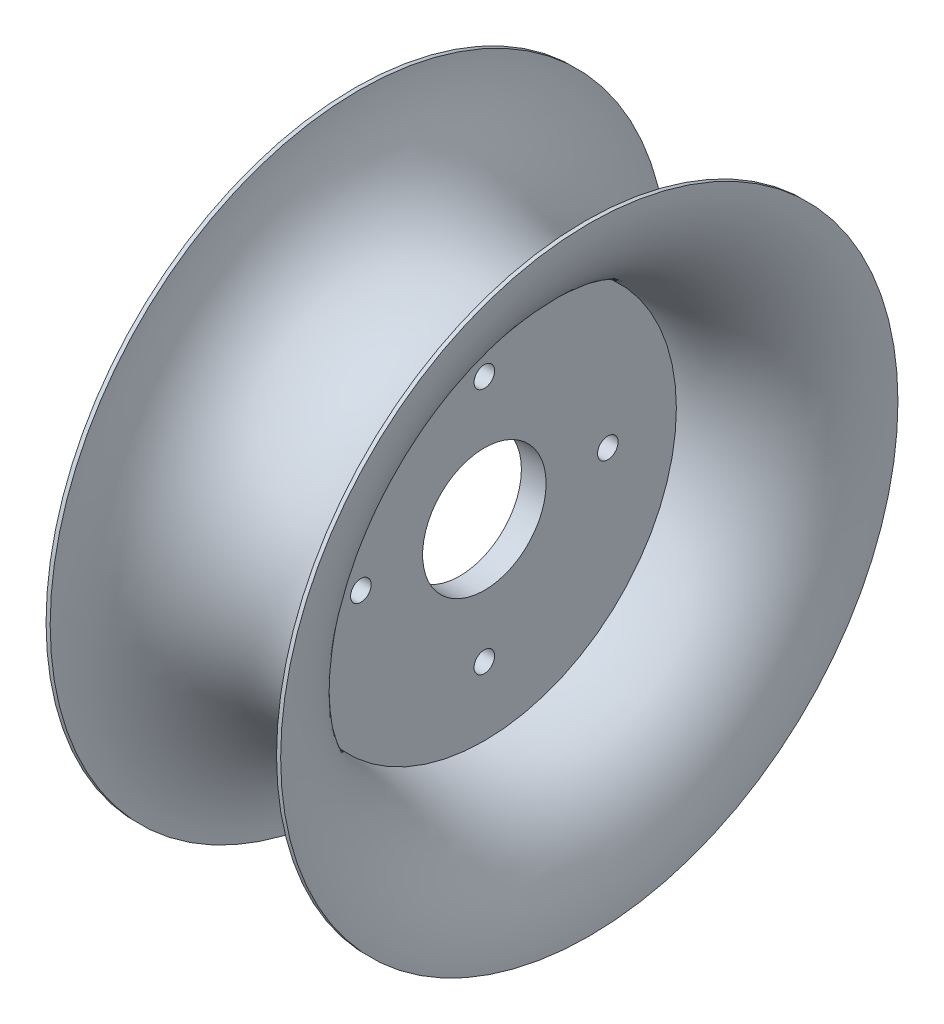
SolidWorks part; units mm, degrees
material "6061-T4 (SS)"
ref_plane "Front Plane" through (0, 0, 0) normal (0, 0, 1) x (1, 0, 0)
ref_plane "Top Plane" through (0, 0, 0) normal (0, 1, 0) x (1, 0, 0)
ref_plane "Right Plane" through (0, 0, 0) normal (1, 0, 0) x (0, 0, -1)
sketch "Sketch1" plane through (0, 0, 0) normal (1, 0, 0) x (0, 0, -1)
  circle A0 centre (0, 0) radius 101.6
  dimension "D1" = 203.2
extrude "Boss-Extrude1" add sketch "Sketch1" along normal mid plane 55
sketch "Sketch2" plane through (0, 0, 0) normal (1, 0, 0) x (0, 0, -1)
  circle A0 centre (0, 0) radius 60
  dimension "D1" = 120
extrude "Cut-Extrude1" cut sketch "Sketch2" against normal blind 500 from offset 3 offset against normal yes
extrude "Cut-Extrude2" cut sketch "Sketch2<2>" along normal blind 500 from offset 3
sketch "Sketch2<2>" plane through (0, 0, 0) normal (1, 0, 0) x (0, 0, -1) same geometry as "Sketch2"
fillet "Fillet1" radius 15 2 edges at (-27.5, 0, -60) (27.5, 0, -60)
fillet "Fillet5" radius 6 2 edges at (27.5, 0, -101.6) (-27.5, 0, -101.6)
sketch "Sketch5" plane through (0, 0, 0) normal (1, 0, 0) x (0, 0, -1)
  line L0 (8.4162, 104.6669) -> (10.4081, 104.4877)
  line L1 (-1, 105) -> (1, 105)
  line L2 (-1, 105) -> (-1, 95)
  line L3 (-1, 95) -> (1, 95)
  line L4 (1, 105) -> (1, 95)
  line L5 (-1, 105) -> (1, 95) construction
  line L6 (-1, 95) -> (1, 105) construction
  line L7 (10.4081, 104.4877) -> (9.5117, 94.5279)
  line L8 (8.4162, 104.6669) -> (7.5198, 94.7072)
  line L9 (7.5198, 94.7072) -> (9.5117, 94.5279)
  line L10 (17.7645, 103.4912) -> (19.7324, 103.134)
  line L11 (19.7324, 103.134) -> (17.9468, 93.2948)
  line L12 (17.7645, 103.4912) -> (15.979, 93.6519)
  line L13 (15.979, 93.6519) -> (17.9468, 93.2948)
  line L14 (26.9699, 101.4821) -> (28.8978, 100.9501)
  line L15 (28.8978, 100.9501) -> (26.2375, 91.3104)
  line L16 (26.9699, 101.4821) -> (24.3095, 91.8425)
  line L17 (24.3095, 91.8425) -> (26.2375, 91.3104)
  line L18 (35.9581, 98.656) -> (37.8306, 97.9533)
  line L19 (37.8306, 97.9533) -> (34.3168, 88.5909)
  line L20 (35.9581, 98.656) -> (32.4444, 89.2937)
  line L21 (32.4444, 89.2937) -> (34.3168, 88.5909)
  line L22 (44.6568, 95.0356) -> (46.4588, 94.1678)
  line L23 (46.4588, 94.1678) -> (42.1199, 85.1582)
  line L24 (44.6568, 95.0356) -> (40.318, 86.0259)
  line L25 (40.318, 86.0259) -> (42.1199, 85.1582)
  line L26 (52.996, 90.65) -> (54.7129, 89.6242)
  line L27 (54.7129, 89.6242) -> (49.5839, 81.0397)
  line L28 (52.996, 90.65) -> (47.867, 82.0655)
  line L29 (47.867, 82.0655) -> (49.5839, 81.0397)
  line L30 (60.9084, 85.5346) -> (62.5265, 84.359)
  line L31 (62.5265, 84.359) -> (56.6486, 76.2688)
  line L32 (60.9084, 85.5346) -> (55.0306, 77.4444)
  line L33 (55.0306, 77.4444) -> (56.6486, 76.2688)
  line L34 (68.3305, 79.7304) -> (69.8366, 78.4146)
  line L35 (69.8366, 78.4146) -> (63.2573, 70.8839)
  line L36 (68.3305, 79.7304) -> (61.7511, 72.1997)
  line L37 (61.7511, 72.1997) -> (63.2573, 70.8839)
  line L38 (75.2024, 73.2844) -> (76.5845, 71.8388)
  line L39 (76.5845, 71.8388) -> (69.3566, 64.9282)
  line L40 (75.2024, 73.2844) -> (67.9744, 66.3737)
  line L41 (67.9744, 66.3737) -> (69.3566, 64.9282)
  line L42 (81.4688, 66.2483) -> (82.7158, 64.6846)
  line L43 (82.7158, 64.6846) -> (74.8975, 58.4497)
  line L44 (81.4688, 66.2483) -> (73.6505, 60.0134)
  line L45 (73.6505, 60.0134) -> (74.8975, 58.4497)
  line L46 (87.0793, 58.6788) -> (88.1811, 57.0096)
  line L47 (88.1811, 57.0096) -> (79.8354, 51.5006)
  line L48 (87.0793, 58.6788) -> (78.7336, 53.1698)
  line L49 (78.7336, 53.1698) -> (79.8354, 51.5006)
  line L50 (91.9887, 50.6368) -> (92.9364, 48.8756)
  line L51 (92.9364, 48.8756) -> (84.1304, 44.1369)
  line L52 (91.9887, 50.6368) -> (83.1827, 45.8981)
  line L53 (83.1827, 45.8981) -> (84.1304, 44.1369)
  line L54 (96.1574, 42.1872) -> (96.9434, 40.3481)
  line L55 (96.9434, 40.3481) -> (87.7482, 36.4179)
  line L56 (96.1574, 42.1872) -> (86.9621, 38.2569)
  line L57 (86.9621, 38.2569) -> (87.7482, 36.4179)
  line L58 (99.5519, 33.3978) -> (100.17, 31.4957)
  line L59 (100.17, 31.4957) -> (90.6594, 28.4056)
  line L60 (99.5519, 33.3978) -> (90.0414, 30.3077)
  line L61 (90.0414, 30.3077) -> (90.6594, 28.4056)
  line L62 (102.1449, 24.3396) -> (102.59, 22.3898)
  line L63 (102.59, 22.3898) -> (92.8407, 20.1646)
  line L64 (102.1449, 24.3396) -> (92.3956, 22.1144)
  line L65 (92.3956, 22.1144) -> (92.8407, 20.1646)
  line L66 (103.9155, 15.0854) -> (104.184, 13.1035)
  line L67 (104.184, 13.1035) -> (94.2745, 11.7612)
  line L68 (103.9155, 15.0854) -> (94.006, 13.7431)
  line L69 (94.006, 13.7431) -> (94.2745, 11.7612)
  line L70 (104.8494, 5.7098) -> (104.9391, 3.7118)
  line L71 (104.9391, 3.7118) -> (94.9492, 3.2632)
  line L72 (104.8494, 5.7098) -> (94.8595, 5.2612)
  line L73 (94.8595, 5.2612) -> (94.9492, 3.2632)
  line L74 (104.9391, -3.7118) -> (104.8494, -5.7098)
  line L75 (104.8494, -5.7098) -> (94.8595, -5.2612)
  line L76 (104.9391, -3.7118) -> (94.9492, -3.2632)
  line L77 (94.9492, -3.2632) -> (94.8595, -5.2612)
  line L78 (104.184, -13.1035) -> (103.9155, -15.0854)
  line L79 (103.9155, -15.0854) -> (94.006, -13.7431)
  line L80 (104.184, -13.1035) -> (94.2745, -11.7612)
  line L81 (94.2745, -11.7612) -> (94.006, -13.7431)
  line L82 (102.59, -22.3898) -> (102.1449, -24.3396)
  line L83 (102.1449, -24.3396) -> (92.3956, -22.1144)
  line L84 (102.59, -22.3898) -> (92.8407, -20.1646)
  line L85 (92.8407, -20.1646) -> (92.3956, -22.1144)
  line L86 (100.17, -31.4957) -> (99.5519, -33.3978)
  line L87 (99.5519, -33.3978) -> (90.0414, -30.3077)
  line L88 (100.17, -31.4957) -> (90.6594, -28.4056)
  line L89 (90.6594, -28.4056) -> (90.0414, -30.3077)
  line L90 (96.9434, -40.3481) -> (96.1574, -42.1872)
  line L91 (96.1574, -42.1872) -> (86.9621, -38.2569)
  line L92 (96.9434, -40.3481) -> (87.7482, -36.4179)
  line L93 (87.7482, -36.4179) -> (86.9621, -38.2569)
  line L94 (92.9364, -48.8756) -> (91.9887, -50.6368)
  line L95 (91.9887, -50.6368) -> (83.1827, -45.8981)
  line L96 (92.9364, -48.8756) -> (84.1304, -44.1369)
  line L97 (84.1304, -44.1369) -> (83.1827, -45.8981)
  line L98 (88.1811, -57.0096) -> (87.0793, -58.6788)
  line L99 (87.0793, -58.6788) -> (78.7336, -53.1698)
  line L100 (88.1811, -57.0096) -> (79.8354, -51.5006)
  line L101 (79.8354, -51.5006) -> (78.7336, -53.1698)
  line L102 (82.7158, -64.6846) -> (81.4688, -66.2483)
  line L103 (81.4688, -66.2483) -> (73.6505, -60.0134)
  line L104 (82.7158, -64.6846) -> (74.8975, -58.4497)
  line L105 (74.8975, -58.4497) -> (73.6505, -60.0134)
  line L106 (76.5845, -71.8388) -> (75.2024, -73.2844)
  line L107 (75.2024, -73.2844) -> (67.9744, -66.3737)
  line L108 (76.5845, -71.8388) -> (69.3566, -64.9282)
  line L109 (69.3566, -64.9282) -> (67.9744, -66.3737)
  line L110 (69.8366, -78.4146) -> (68.3305, -79.7304)
  line L111 (68.3305, -79.7304) -> (61.7511, -72.1997)
  line L112 (69.8366, -78.4146) -> (63.2573, -70.8839)
  line L113 (63.2573, -70.8839) -> (61.7511, -72.1997)
  line L114 (62.5265, -84.359) -> (60.9084, -85.5346)
  line L115 (60.9084, -85.5346) -> (55.0306, -77.4444)
  line L116 (62.5265, -84.359) -> (56.6486, -76.2688)
  line L117 (56.6486, -76.2688) -> (55.0306, -77.4444)
  line L118 (54.7129, -89.6242) -> (52.996, -90.65)
  line L119 (52.996, -90.65) -> (47.867, -82.0655)
  line L120 (54.7129, -89.6242) -> (49.5839, -81.0397)
  line L121 (49.5839, -81.0397) -> (47.867, -82.0655)
  line L122 (46.4588, -94.1678) -> (44.6568, -95.0356)
  line L123 (44.6568, -95.0356) -> (40.318, -86.0259)
  line L124 (46.4588, -94.1678) -> (42.1199, -85.1582)
  line L125 (42.1199, -85.1582) -> (40.318, -86.0259)
  line L126 (37.8306, -97.9533) -> (35.9581, -98.656)
  line L127 (35.9581, -98.656) -> (32.4444, -89.2937)
  line L128 (37.8306, -97.9533) -> (34.3168, -88.5909)
  line L129 (34.3168, -88.5909) -> (32.4444, -89.2937)
  line L130 (28.8978, -100.9501) -> (26.9699, -101.4821)
  line L131 (26.9699, -101.4821) -> (24.3095, -91.8425)
  line L132 (28.8978, -100.9501) -> (26.2375, -91.3104)
  line L133 (26.2375, -91.3104) -> (24.3095, -91.8425)
  line L134 (19.7324, -103.134) -> (17.7645, -103.4912)
  line L135 (17.7645, -103.4912) -> (15.979, -93.6519)
  line L136 (19.7324, -103.134) -> (17.9468, -93.2948)
  line L137 (17.9468, -93.2948) -> (15.979, -93.6519)
  line L138 (10.4081, -104.4877) -> (8.4162, -104.6669)
  line L139 (8.4162, -104.6669) -> (7.5198, -94.7072)
  line L140 (10.4081, -104.4877) -> (9.5117, -94.5279)
  line L141 (9.5117, -94.5279) -> (7.5198, -94.7072)
  line L142 (1, -105) -> (-1, -105)
  line L143 (-1, -105) -> (-1, -95)
  line L144 (1, -105) -> (1, -95)
  line L145 (1, -95) -> (-1, -95)
  line L146 (-8.4162, -104.6669) -> (-10.4081, -104.4877)
  line L147 (-10.4081, -104.4877) -> (-9.5117, -94.5279)
  line L148 (-8.4162, -104.6669) -> (-7.5198, -94.7072)
  line L149 (-7.5198, -94.7072) -> (-9.5117, -94.5279)
  line L150 (-17.7645, -103.4912) -> (-19.7324, -103.134)
  line L151 (-19.7324, -103.134) -> (-17.9468, -93.2948)
  line L152 (-17.7645, -103.4912) -> (-15.979, -93.6519)
  line L153 (-15.979, -93.6519) -> (-17.9468, -93.2948)
  line L154 (-26.9699, -101.4821) -> (-28.8978, -100.9501)
  line L155 (-28.8978, -100.9501) -> (-26.2375, -91.3104)
  line L156 (-26.9699, -101.4821) -> (-24.3095, -91.8425)
  line L157 (-24.3095, -91.8425) -> (-26.2375, -91.3104)
  line L158 (-35.9581, -98.656) -> (-37.8306, -97.9533)
  line L159 (-37.8306, -97.9533) -> (-34.3168, -88.5909)
  line L160 (-35.9581, -98.656) -> (-32.4444, -89.2937)
  line L161 (-32.4444, -89.2937) -> (-34.3168, -88.5909)
  line L162 (-44.6568, -95.0356) -> (-46.4588, -94.1678)
  line L163 (-46.4588, -94.1678) -> (-42.1199, -85.1582)
  line L164 (-44.6568, -95.0356) -> (-40.318, -86.0259)
  line L165 (-40.318, -86.0259) -> (-42.1199, -85.1582)
  line L166 (-52.996, -90.65) -> (-54.7129, -89.6242)
  line L167 (-54.7129, -89.6242) -> (-49.5839, -81.0397)
  line L168 (-52.996, -90.65) -> (-47.867, -82.0655)
  line L169 (-47.867, -82.0655) -> (-49.5839, -81.0397)
  line L170 (-60.9084, -85.5346) -> (-62.5265, -84.359)
  line L171 (-62.5265, -84.359) -> (-56.6486, -76.2688)
  line L172 (-60.9084, -85.5346) -> (-55.0306, -77.4444)
  line L173 (-55.0306, -77.4444) -> (-56.6486, -76.2688)
  line L174 (-68.3305, -79.7304) -> (-69.8366, -78.4146)
  line L175 (-69.8366, -78.4146) -> (-63.2573, -70.8839)
  line L176 (-68.3305, -79.7304) -> (-61.7511, -72.1997)
  line L177 (-61.7511, -72.1997) -> (-63.2573, -70.8839)
  line L178 (-75.2024, -73.2844) -> (-76.5845, -71.8388)
  line L179 (-76.5845, -71.8388) -> (-69.3566, -64.9282)
  line L180 (-75.2024, -73.2844) -> (-67.9744, -66.3737)
  line L181 (-67.9744, -66.3737) -> (-69.3566, -64.9282)
  line L182 (-81.4688, -66.2483) -> (-82.7158, -64.6846)
  line L183 (-82.7158, -64.6846) -> (-74.8975, -58.4497)
  line L184 (-81.4688, -66.2483) -> (-73.6505, -60.0134)
  line L185 (-73.6505, -60.0134) -> (-74.8975, -58.4497)
  line L186 (-87.0793, -58.6788) -> (-88.1811, -57.0096)
  line L187 (-88.1811, -57.0096) -> (-79.8354, -51.5006)
  line L188 (-87.0793, -58.6788) -> (-78.7336, -53.1698)
  line L189 (-78.7336, -53.1698) -> (-79.8354, -51.5006)
  line L190 (-91.9887, -50.6368) -> (-92.9364, -48.8756)
  line L191 (-92.9364, -48.8756) -> (-84.1304, -44.1369)
  line L192 (-91.9887, -50.6368) -> (-83.1827, -45.8981)
  line L193 (-83.1827, -45.8981) -> (-84.1304, -44.1369)
  line L194 (-96.1574, -42.1872) -> (-96.9434, -40.3481)
  line L195 (-96.9434, -40.3481) -> (-87.7482, -36.4179)
  line L196 (-96.1574, -42.1872) -> (-86.9621, -38.2569)
  line L197 (-86.9621, -38.2569) -> (-87.7482, -36.4179)
  line L198 (-99.5519, -33.3978) -> (-100.17, -31.4957)
  line L199 (-100.17, -31.4957) -> (-90.6594, -28.4056)
  line L200 (-99.5519, -33.3978) -> (-90.0414, -30.3077)
  line L201 (-90.0414, -30.3077) -> (-90.6594, -28.4056)
  line L202 (-102.1449, -24.3396) -> (-102.59, -22.3898)
  line L203 (-102.59, -22.3898) -> (-92.8407, -20.1646)
  line L204 (-102.1449, -24.3396) -> (-92.3956, -22.1144)
  line L205 (-92.3956, -22.1144) -> (-92.8407, -20.1646)
  line L206 (-103.9155, -15.0854) -> (-104.184, -13.1035)
  line L207 (-104.184, -13.1035) -> (-94.2745, -11.7612)
  line L208 (-103.9155, -15.0854) -> (-94.006, -13.7431)
  line L209 (-94.006, -13.7431) -> (-94.2745, -11.7612)
  line L210 (-104.8494, -5.7098) -> (-104.9391, -3.7118)
  line L211 (-104.9391, -3.7118) -> (-94.9492, -3.2632)
  line L212 (-104.8494, -5.7098) -> (-94.8595, -5.2612)
  line L213 (-94.8595, -5.2612) -> (-94.9492, -3.2632)
  line L214 (-104.9391, 3.7118) -> (-104.8494, 5.7098)
  line L215 (-104.8494, 5.7098) -> (-94.8595, 5.2612)
  line L216 (-104.9391, 3.7118) -> (-94.9492, 3.2632)
  line L217 (-94.9492, 3.2632) -> (-94.8595, 5.2612)
  line L218 (-104.184, 13.1035) -> (-103.9155, 15.0854)
  line L219 (-103.9155, 15.0854) -> (-94.006, 13.7431)
  line L220 (-104.184, 13.1035) -> (-94.2745, 11.7612)
  line L221 (-94.2745, 11.7612) -> (-94.006, 13.7431)
  line L222 (-102.59, 22.3898) -> (-102.1449, 24.3396)
  line L223 (-102.1449, 24.3396) -> (-92.3956, 22.1144)
  line L224 (-102.59, 22.3898) -> (-92.8407, 20.1646)
  line L225 (-92.8407, 20.1646) -> (-92.3956, 22.1144)
  line L226 (-100.17, 31.4957) -> (-99.5519, 33.3978)
  line L227 (-99.5519, 33.3978) -> (-90.0414, 30.3077)
  line L228 (-100.17, 31.4957) -> (-90.6594, 28.4056)
  line L229 (-90.6594, 28.4056) -> (-90.0414, 30.3077)
  line L230 (-96.9434, 40.3481) -> (-96.1574, 42.1872)
  line L231 (-96.1574, 42.1872) -> (-86.9621, 38.2569)
  line L232 (-96.9434, 40.3481) -> (-87.7482, 36.4179)
  line L233 (-87.7482, 36.4179) -> (-86.9621, 38.2569)
  line L234 (-92.9364, 48.8756) -> (-91.9887, 50.6368)
  line L235 (-91.9887, 50.6368) -> (-83.1827, 45.8981)
  line L236 (-92.9364, 48.8756) -> (-84.1304, 44.1369)
  line L237 (-84.1304, 44.1369) -> (-83.1827, 45.8981)
  line L238 (-88.1811, 57.0096) -> (-87.0793, 58.6788)
  line L239 (-87.0793, 58.6788) -> (-78.7336, 53.1698)
  line L240 (-88.1811, 57.0096) -> (-79.8354, 51.5006)
  line L241 (-79.8354, 51.5006) -> (-78.7336, 53.1698)
  line L242 (-82.7158, 64.6846) -> (-81.4688, 66.2483)
  line L243 (-81.4688, 66.2483) -> (-73.6505, 60.0134)
  line L244 (-82.7158, 64.6846) -> (-74.8975, 58.4497)
  line L245 (-74.8975, 58.4497) -> (-73.6505, 60.0134)
  line L246 (-76.5845, 71.8388) -> (-75.2024, 73.2844)
  line L247 (-75.2024, 73.2844) -> (-67.9744, 66.3737)
  line L248 (-76.5845, 71.8388) -> (-69.3566, 64.9282)
  line L249 (-69.3566, 64.9282) -> (-67.9744, 66.3737)
  line L250 (-69.8366, 78.4146) -> (-68.3305, 79.7304)
  line L251 (-68.3305, 79.7304) -> (-61.7511, 72.1997)
  line L252 (-69.8366, 78.4146) -> (-63.2573, 70.8839)
  line L253 (-63.2573, 70.8839) -> (-61.7511, 72.1997)
  line L254 (-62.5265, 84.359) -> (-60.9084, 85.5346)
  line L255 (-60.9084, 85.5346) -> (-55.0306, 77.4444)
  line L256 (-62.5265, 84.359) -> (-56.6486, 76.2688)
  line L257 (-56.6486, 76.2688) -> (-55.0306, 77.4444)
  line L258 (-54.7129, 89.6242) -> (-52.996, 90.65)
  line L259 (-52.996, 90.65) -> (-47.867, 82.0655)
  line L260 (-54.7129, 89.6242) -> (-49.5839, 81.0397)
  line L261 (-49.5839, 81.0397) -> (-47.867, 82.0655)
  line L262 (-46.4588, 94.1678) -> (-44.6568, 95.0356)
  line L263 (-44.6568, 95.0356) -> (-40.318, 86.0259)
  line L264 (-46.4588, 94.1678) -> (-42.1199, 85.1582)
  line L265 (-42.1199, 85.1582) -> (-40.318, 86.0259)
  line L266 (-37.8306, 97.9533) -> (-35.9581, 98.656)
  line L267 (-35.9581, 98.656) -> (-32.4444, 89.2937)
  line L268 (-37.8306, 97.9533) -> (-34.3168, 88.5909)
  line L269 (-34.3168, 88.5909) -> (-32.4444, 89.2937)
  line L270 (-28.8978, 100.9501) -> (-26.9699, 101.4821)
  line L271 (-26.9699, 101.4821) -> (-24.3095, 91.8425)
  line L272 (-28.8978, 100.9501) -> (-26.2375, 91.3104)
  line L273 (-26.2375, 91.3104) -> (-24.3095, 91.8425)
  line L274 (-19.7324, 103.134) -> (-17.7645, 103.4912)
  line L275 (-17.7645, 103.4912) -> (-15.979, 93.6519)
  line L276 (-19.7324, 103.134) -> (-17.9468, 93.2948)
  line L277 (-17.9468, 93.2948) -> (-15.979, 93.6519)
  line L278 (-10.4081, 104.4877) -> (-8.4162, 104.6669)
  line L279 (-8.4162, 104.6669) -> (-7.5198, 94.7072)
  line L280 (-10.4081, 104.4877) -> (-9.5117, 94.5279)
  line L281 (-9.5117, 94.5279) -> (-7.5198, 94.7072)
  circle A0 centre (0, 0) radius 100
  point P3 (0, 100)
  point P10 (0, 95)
  point P286 (0, 0)
  point P287 (-8.5157, 94.6176)
  dimension "D1" = 200
  dimension "D2" = 2
  dimension "D3" = 10
  dimension "D5" = 8.5157
  dimension "D4" = 70
sketch "Sketch6" plane through (3, 0, 0) normal (1, 0, 0) x (0, 0, -1)
  circle A0 centre (0, 0) radius 15
  dimension "D1" = 30
extrude "Cut-Extrude4" cut sketch "Sketch5" against normal mid plane 52 contours L15 L17 L16 L14 | L11 L13 L12 L10 | L7 L9 L8 L0 | L4 L3 L2 L1 | L279 L281 L280 L278 | L275 L277 L276 L274 | L19 L21 L20 L18 | L24 L25 L23 L22 | L27 L29 L28 L26 | L32 L33 L31 L30 | L36 L37 L35 L34 | L40 L41 L39 L38 | L44 L45 L43 L42 | L46 L47 L49 L48 | L52 L53 L51 L50 | L56 L57 L55 L54 | L60 L61 L59 L58 | L63 L65 L64 L62 | L68 L69 L67 L66 | L72 L73 L71 L70 | L75 L77 L76 L74 | L79 L81 L80 L78 | L271 L273 L272 L270 | L267 L269 L268 L266 | L263 L265 L264 L262 | L259 L261 L260 L258 | L256 L257 L255 L254 | L251 L253 L252 L250 | L247 L249 L248 L246 | L243 L245 L244 L242 | L238 L239 L241 L240 | L235 L237 L236 L234 | L231 L233 L232 L230 | L227 L229 L228 L226 | L223 L225 L224 L222 | L219 L221 L220 L218 | L216 L217 L215 L214 | L211 L213 L212 L210 | L207 L209 L208 L206 | L203 L205 L204 L202 | L199 L201 L200 L198 | L195 L197 L196 L194 | L191 L193 L192 L190 | L83 L85 L84 L82 | L87 L89 L88 L86 | L91 L93 L92 L90 | L95 L97 L96 L94 | L99 L101 L100 L98 | L103 L105 L104 L102 | L106 L107 L109 L108 | L112 L113 L111 L110 | L115 L117 L116 L114 | L119 L121 L120 L118 | L123 L125 L124 L122 | L127 L129 L128 L126 | L131 L133 L132 L130 | L135 L137 L136 L134 | L139 L141 L140 L138 | L143 L145 L144 L142 | L147 L149 L148 L146 | L151 L153 L152 L150 | L155 L157 L156 L154 | L159 L161 L160 L158 | L163 L165 L164 L162 | L167 L169 L168 L166 | L171 L173 L172 L170 | L175 L177 L176 L174 | L179 L181 L180 L178 | L183 L185 L184 L182 | L187 L189 L188 L186
extrude "Cut-Extrude5" cut sketch "Sketch6" against normal mid plane 48
sketch "Sketch7" plane through (-3, 0, 0) normal (-1, 0, 0) x (0, 0, 1)
  circle A0 centre (30, 0) radius 2.5
  circle A1 centre (0, -30) radius 2.5
  circle A2 centre (-30, 0) radius 2.5
  circle A3 centre (0, 30) radius 2.5
  point P12 (0, 0)
  dimension "D1" = 5
  dimension "D2" = 30
  dimension "D4" = 30
  dimension "D3" = 4
extrude "Cut-Extrude6" cut sketch "Sketch7" against normal mid plane 48
sketch "Sketch8" plane through (0, 0, 0) normal (1, 0, 0) x (0, 0, -1)
  circle A1 centre (0, 0) radius 127.5039
  circle A2 centre (0, 0) radius 75
  dimension "D1" = 150
  dimension "D2" = 255.0078
extrude "Cut-Extrude7" cut sketch "Sketch8" against normal mid plane 70 contours A1 | A2
sketch "Sketch9" plane through (0, 0, 0) normal (0, 1, 0) x (1, 0, 0)
  line L1 (0, -101.6) -> (0, 101.6) construction
  line L2 (-37.6622, 0) -> (85.3471, 0) construction
  circle A1 centre (0, 75) radius 28.5
  dimension "D1" = 57
  dimension "D2" = 75
revolve "Revolve1" add sketch "Sketch9" angle 360 about L2
sketch "Sketch10" plane through (0, 0, 0) normal (0, 1, 0) x (1, 0, 0)
  line L0 (0, -101.6) -> (0, 101.6) construction
  line L1 (-77.7522, 0) -> (153.0376, 0) construction
  line L2 (-40, 109.762) -> (40, 109.762)
  line L3 (-40, 109.762) -> (-40, 74.998)
  line L4 (-40, 74.998) -> (40, 74.998)
  line L5 (40, 109.762) -> (40, 74.998)
  line L6 (-40, 109.762) -> (40, 74.998) construction
  line L7 (-40, 74.998) -> (40, 109.762) construction
  circle A0 centre (0, 75) radius 27.5
  point P4 (0, 92.38)
  dimension "D1" = 55
  dimension "D2" = 75
  dimension "D3" = 80
  dimension "D4" = 34.7641
  dimension "D5" = 92.38
revolve "Cut-Revolve1" cut sketch "Sketch10" angle 360 about L1 region at (0, 0, -108.8898) region at (0, 0, -86.6703) region at (0, 0, -63.3275)
